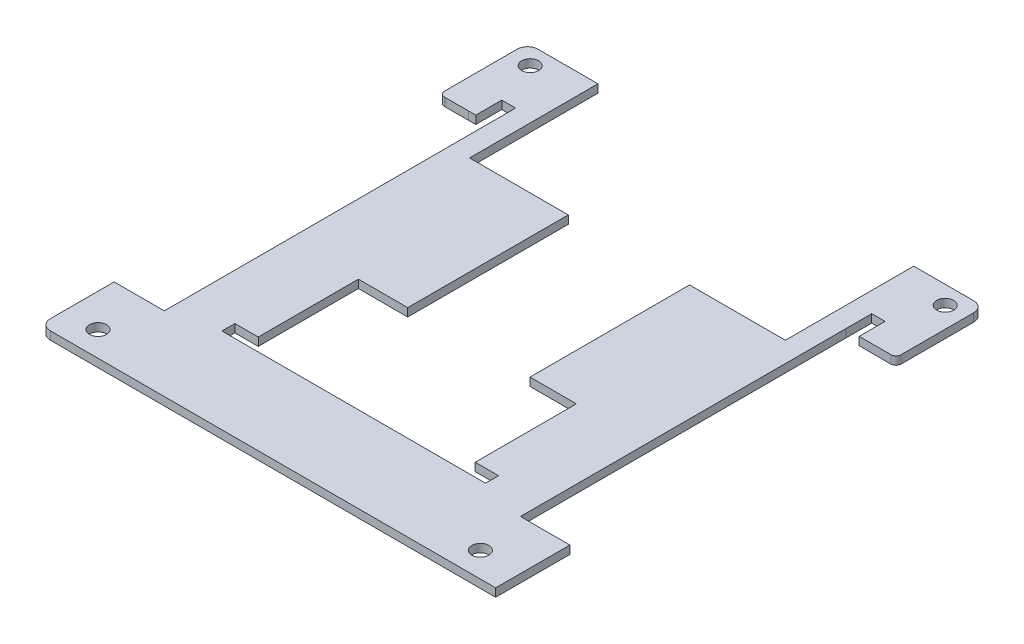
SolidWorks part; units mm, degrees
note: The reader was unsure of these and kept them because the rebuilt part matched: shared geometry of "Sketch1<2>".
material "Copper"
ref_plane "Front Plane" through (0, 0, 0) normal (0, 0, 1) x (1, 0, 0)
ref_plane "Top Plane" through (0, 0, 0) normal (0, 1, 0) x (1, 0, 0)
ref_plane "Right Plane" through (0, 0, 0) normal (1, 0, 0) x (0, 0, -1)
sketch "Sketch1" plane through (0, 0, 0) normal (0, 1, 0) x (1, 0, 0)
  line L0 (-38.395, 30) -> (-42.73, 30)
  line L1 (-44, 31.27) -> (-44, 45)
  line L2 (42, 47) -> (30.435, 47)
  line L3 (44, 45) -> (44, 32)
  line L4 (44, 32) -> (44, 31.0156)
  line L5 (42.9984, 30.0156) -> (33.8256, 30.0304)
  line L6 (32.824, 29.0304) -> (32.824, -30.454)
  line L7 (-44, -38.977) -> (-44, -32.454)
  line L8 (-42, -47) -> (43.8497, -47)
  line L9 (-44, -45) -> (-44, -38.977)
  line L10 (-43, -31.454) -> (-36.1, -31.454)
  line L11 (43.8497, -37) -> (43.8497, -32.454)
  line L12 (42.8497, -31.454) -> (36.1, -31.454)
  line L13 (23.409, -31.5) -> (-23.409, -31.5)
  line L14 (-11.409, -9.9) -> (-23.409, -9.9)
  line L15 (30.435, 22.2554) -> (11.9708, 22.2554)
  line L16 (-11.409, -9.9) -> (-11.409, 22.2554)
  line L17 (30.435, 47) -> (30.435, 22.2554)
  line L18 (11.9708, 22.2554) -> (11.9708, -8.5)
  line L19 (-23.409, -31.5) -> (-23.409, -9.9)
  line L20 (11.9708, -8.5) -> (23.409, -8.5)
  line L21 (-36.1, -31.454) -> (-33.824, -31.454)
  line L22 (-32.824, -30.454) -> (-32.824, 29.0115)
  line L23 (-33.8265, 30.0115) -> (-38.395, 30)
  line L24 (-42.73, 30) -> (-43.011, 30.0031)
  line L25 (-44, 31.003) -> (-44, 31.27)
  line L28 (43.8497, -47) -> (43.8497, -37)
  line L33 (33.824, -31.454) -> (36.1, -31.454)
  line L34 (-23.409, 13.2954) -> (-23.409, -31.5) construction
  line L35 (23.409, -31.5) -> (23.409, -8.5)
  line L41 (-42, 47) -> (-30.435, 47)
  line L42 (-30.435, 47) -> (-30.435, 22.2554)
  line L43 (-30.435, 22.2554) -> (-11.409, 22.2554)
  circle A0 centre (40, 43.5) radius 1.6383
  circle A1 centre (-40, 43.5) radius 1.6383
  circle A2 centre (-37.6, -42.2) radius 1.6383
  circle A3 centre (36.1, -42.2) radius 1.6383
  arc A5 (-42, 47) -> (-44, 45) centre (-42, 45) ccw
  arc A6 (44, 45) -> (42, 47) centre (42, 45) ccw
  arc A9 (-43.011, 30.0031) -> (-44, 31.003) centre (-43, 31.003) cw
  arc A10 (-32.824, 29.0115) -> (-33.8265, 30.0115) centre (-33.824, 29.0115) ccw
  arc A11 (-44, -45) -> (-42, -47) centre (-42, -45) ccw
  arc A12 (44, 31.0156) -> (42.9984, 30.0156) centre (43, 31.0156) cw
  arc A14 (33.8256, 30.0304) -> (32.824, 29.0304) centre (33.824, 29.0304) ccw
  arc A15 (43.8497, -32.454) -> (42.8497, -31.454) centre (42.8497, -32.454) ccw
  arc A16 (32.824, -30.454) -> (33.824, -31.454) centre (33.824, -30.454) ccw
  arc A17 (-33.824, -31.454) -> (-32.824, -30.454) centre (-33.824, -30.454) ccw
  arc A18 (-44, -32.454) -> (-43, -31.454) centre (-43, -32.454) cw
  point P37 (-44, 30.014)
  point P48 (-32.824, 30.014)
  point P61 (44, 30.014)
  point P80 (32.824, 30.032)
  point P95 (32.824, -31.454)
  point P98 (-32.824, -31.454)
  dimension "D1" = 1
  dimension "D2" = 73.7
  dimension "D3" = 85.7
  dimension "D4" = 80
  dimension "D5" = 85.7
  dimension "D6" = 19.026
  dimension "D7" = 12
  dimension "D8" = 18.4641
  dimension "D9" = 11.4381
  dimension "D10" = 32.1554
  dimension "D11" = 21.6
extrude "Boss-Extrude1" [suppressed] add sketch "Sketch1" along normal blind 1.575
extrude "Boss-Extrude2" add sketch "Sketch1<2>" along normal blind 1.575
sketch "Sketch1<2>" plane through (0, 0, 0) normal (0, 1, 0) x (1, 0, 0) same geometry as "Sketch1"
sketch "Sketch2" plane through (0, 1.575, 0) normal (0, 1, 0) x (1, 0, 0)
  line L1 (32.8227, -32.694) -> (46.9034, -32.694)
  line L2 (32.8227, -32.694) -> (32.8227, -25.5777)
  line L3 (32.8227, -25.5777) -> (46.9034, -25.5777)
  line L4 (46.9034, -32.694) -> (46.9034, -25.5777)
  line L5 (-47.8402, -23.2727) -> (-32.833, -23.2727)
  line L6 (-47.8402, -23.2727) -> (-47.8402, -32.694)
  line L7 (-47.8402, -32.694) -> (-32.833, -32.694)
  line L8 (-32.833, -23.2727) -> (-32.833, -32.694)
  dimension "D1" = 14.306
  dimension "D2" = 11.027
  dimension "D3" = 11.167
  dimension "D4" = 14.306
extrude "Cut-Extrude1" cut sketch "Sketch2" against normal through all
sketch "Additional PCB material" plane through (0, 1.575, 0) normal (0, 1, 0) x (1, 0, 0)
  line L0 (32.824, 29.0304) -> (32.824, -30.454) construction
  line L1 (31.6745, 31.4781) -> (34.324, 31.4781)
  line L2 (31.6745, 31.4781) -> (31.6745, -33.7352)
  line L3 (31.6745, -33.7352) -> (34.324, -33.7352)
  line L4 (34.324, 31.4781) -> (34.324, -33.7352)
  line L5 (-34.324, 31.564) -> (-32.824, 31.564)
  line L6 (-34.324, 31.564) -> (-34.324, -33.7352)
  line L7 (-34.324, -33.7352) -> (-32.824, -33.7352)
  line L8 (-32.824, 31.564) -> (-32.824, -33.7352)
  dimension "D1" = 1.5
  dimension "D2" = 1.5
  dimension "D3" = 1.5
extrude "Boss-Extrude3" add sketch "Additional PCB material" against normal blind 1.575
sketch "Sketch3" plane through (0, 1.575, 0) normal (0, 1, 0) x (1, 0, 0)
  line L0 (23.409, -31.5) -> (23.409, -8.5) construction
  line L1 (-23.409, -31.5) -> (23.409, -31.5)
  line L2 (-23.409, -31.5) -> (-23.409, -30.5)
  line L3 (-23.409, -30.5) -> (23.409, -30.5)
  line L4 (23.409, -31.5) -> (23.409, -30.5)
  dimension "D1" = 1
extrude "Boss-Extrude4" add sketch "Sketch3" against normal blind 1.575
sketch "Sketch4" plane through (0, 1.575, 0) normal (0, 1, 0) x (1, 0, 0)
  line L1 (23.409, -30.5) -> (25.409, -30.5)
  line L2 (23.409, -30.5) -> (23.409, -28)
  line L3 (23.409, -28) -> (25.409, -28)
  line L4 (25.409, -30.5) -> (25.409, -28)
  line L5 (-23.409, -30.5) -> (-25.409, -30.5)
  line L6 (-23.409, -30.5) -> (-23.409, -28)
  line L7 (-23.409, -28) -> (-25.409, -28)
  line L8 (-25.409, -30.5) -> (-25.409, -28)
  dimension "D1" = 2.5
  dimension "D2" = 2
  dimension "D3" = 2.5
  dimension "D4" = 2
extrude "Cut-Extrude2" cut sketch "Sketch4" against normal through all
sketch "Sketch5" plane through (0, 1.575, 0) normal (0, 1, 0) x (1, 0, 0)
  line L0 (-11.409, -9.9) -> (-23.409, -9.9) construction
  line L1 (-23.409, -28) -> (-20.909, -28)
  line L2 (-23.409, -28) -> (-23.409, -9.9)
  line L3 (-23.409, -9.9) -> (-20.909, -9.9)
  line L4 (-20.909, -28) -> (-20.909, -9.9)
  line L5 (11.9708, -8.5) -> (23.409, -8.5) construction
  line L6 (23.409, -28) -> (20.909, -28)
  line L7 (23.409, -28) -> (23.409, -8.5)
  line L8 (23.409, -8.5) -> (20.909, -8.5)
  line L9 (20.909, -28) -> (20.909, -8.5)
  dimension "D1" = 2.5
  dimension "D2" = 2.5
extrude "Boss-Extrude5" add sketch "Sketch5" against normal blind 1.575
sketch "Sketch7" plane through (0, 1.575, 0) normal (0, 1, 0) x (1, 0, 0)
  line L1 (-11.409, -9.9) -> (-20.909, -9.9)
  line L2 (-11.409, -9.9) -> (-11.409, -8.694)
  line L3 (-11.409, -8.694) -> (-20.909, -8.694)
  line L4 (-20.909, -9.9) -> (-20.909, -8.694)
  dimension "D1" = 24
extrude "Cut-Extrude3" cut sketch "Sketch7" against normal through all
hole_wizard "M3 Clearance Hole1" [suppressed] positions "Sketch8" profile "Sketch9" hole size "M3" standard "ISO"
sketch "Sketch8" plane through (-37.3577, 1.575, 48.2358) normal (0, 1, 0) x (-1, 0, 0)
  point P0 (-23.5587, -42.7243)
  point P1 (-23.5587, -67.2443)
  point P2 (-7.0387, -67.2443)
  point P3 (-7.0387, -42.7243)
sketch "Sketch9" plane through (-13.799, 1.575, 5.5115) normal (1, 0, 0) x (0, 0, 1)
  line L0 (0, 0) -> (0, 1.575)
  line L1 (0, 1.575) -> (1.6, 1.575)
  line L2 (1.6, 1.575) -> (1.6, 0)
  line L3 (1.6, 0) -> (0, 0)
  line L4 (0, -6.35) -> (0, 107.95) construction
  dimension "Thru Hole Dia." = 3.2
  dimension "Thru Hole Depth" = 1.575
hole_wizard "M3 Clearance Hole2" [suppressed] positions "Sketch18" profile "Sketch19" hole size "M3" standard "ISO"
sketch "Sketch18" plane through (-37.3577, 1.575, 48.2358) normal (0, 1, 0) x (-1, 0, 0)
  point P0 (-51.7186, -42.7243)
sketch "Sketch19" plane through (14.3608, 1.575, 5.5115) normal (1, 0, 0) x (0, 0, 1)
  line L0 (0, 0) -> (0, 1.575)
  line L1 (0, 1.575) -> (1.6, 1.575)
  line L2 (1.6, 1.575) -> (1.6, 0)
  line L3 (1.6, 0) -> (0, 0)
  line L4 (0, -6.35) -> (0, 107.95) construction
  dimension "Thru Hole Dia." = 3.2
  dimension "Thru Hole Depth" = 1.575
hole_wizard "M3 Clearance Hole3" [suppressed] positions "Sketch20" profile "Sketch21" hole size "M3" standard "ISO"
sketch "Sketch20" plane through (-37.3577, 1.575, 48.2358) normal (0, 1, 0) x (-1, 0, 0)
  point P2 (-68.2386, -42.7243)
sketch "Sketch21" plane through (30.8808, 1.575, 5.5115) normal (1, 0, 0) x (0, 0, 1)
  line L0 (0, 0) -> (0, 1.575)
  line L1 (0, 1.575) -> (1.6, 1.575)
  line L2 (1.6, 1.575) -> (1.6, 0)
  line L3 (1.6, 0) -> (0, 0)
  line L4 (0, -6.35) -> (0, 107.95) construction
  dimension "Thru Hole Dia." = 3.2
  dimension "Thru Hole Depth" = 1.575
hole_wizard "M3 Clearance Hole4" [suppressed] positions "Sketch22" profile "Sketch23" hole size "M3" standard "ISO"
sketch "Sketch22" plane through (-37.3577, 21.15, 48.2358) normal (0, 1, 0) x (-1, 0, 0)
  point P0 (-51.7186, -67.2443)
sketch "Sketch23" plane through (14.3608, 21.15, -19.0085) normal (1, 0, 0) x (0, 0, 1)
  line L0 (0, 0) -> (0, 21.15)
  line L1 (0, 21.15) -> (1.6, 21.15)
  line L2 (1.6, 21.15) -> (1.6, 0)
  line L3 (1.6, 0) -> (0, 0)
  line L4 (0, -6.35) -> (0, 107.95) construction
  dimension "Thru Hole Dia." = 3.2
  dimension "Thru Hole Depth" = 21.15
hole_wizard "M3 Clearance Hole5" [suppressed] positions "Sketch24" profile "Sketch25" hole size "M3" standard "ISO"
sketch "Sketch24" plane through (-37.3577, 1.575, 48.2358) normal (0, 1, 0) x (-1, 0, 0)
  point P0 (-68.2386, -67.2443)
sketch "Sketch25" plane through (30.8808, 1.575, -19.0085) normal (1, 0, 0) x (0, 0, 1)
  line L0 (0, 0) -> (0, 1.575)
  line L1 (0, 1.575) -> (1.6, 1.575)
  line L2 (1.6, 1.575) -> (1.6, 0)
  line L3 (1.6, 0) -> (0, 0)
  line L4 (0, -6.35) -> (0, 107.95) construction
  dimension "Thru Hole Dia." = 3.2
  dimension "Thru Hole Depth" = 1.575
sketch "Sketch26" plane through (0, 1.575, 0) normal (0, 1, 0) x (1, 0, 0)
  line L0 (44, 45) -> (44, 32) construction
  line L1 (-36.984, 35.0102) -> (-34.324, 35.0102)
  line L2 (-36.984, 35.0102) -> (-36.984, 30.0102)
  line L3 (-34.324, 29.9278) -> (-36.984, 29.9278)
  line L4 (-34.324, 30.0102) -> (-34.324, -32.694) construction
  line L5 (34.325, 35.0156) -> (36.9, 35.0156)
  line L6 (34.325, 35.0156) -> (34.325, 30.0156)
  line L7 (34.325, 30.0156) -> (36.9, 30.0156)
  line L8 (36.9, 35.0156) -> (36.9, 30.0156)
  line L9 (-34.324, 35.0102) -> (-34.324, 29.9278)
  line L10 (-36.984, 30.0102) -> (-36.984, 29.9278)
  dimension "D1" = 7.016
  dimension "D3" = 7.1
  dimension "D4" = 5
  dimension "D5" = 2.575
  dimension "D6" = 5
  dimension "D7" = 5
  dimension "D8" = 0
extrude "Cut-Extrude4" cut sketch "Sketch26" against normal blind 10
